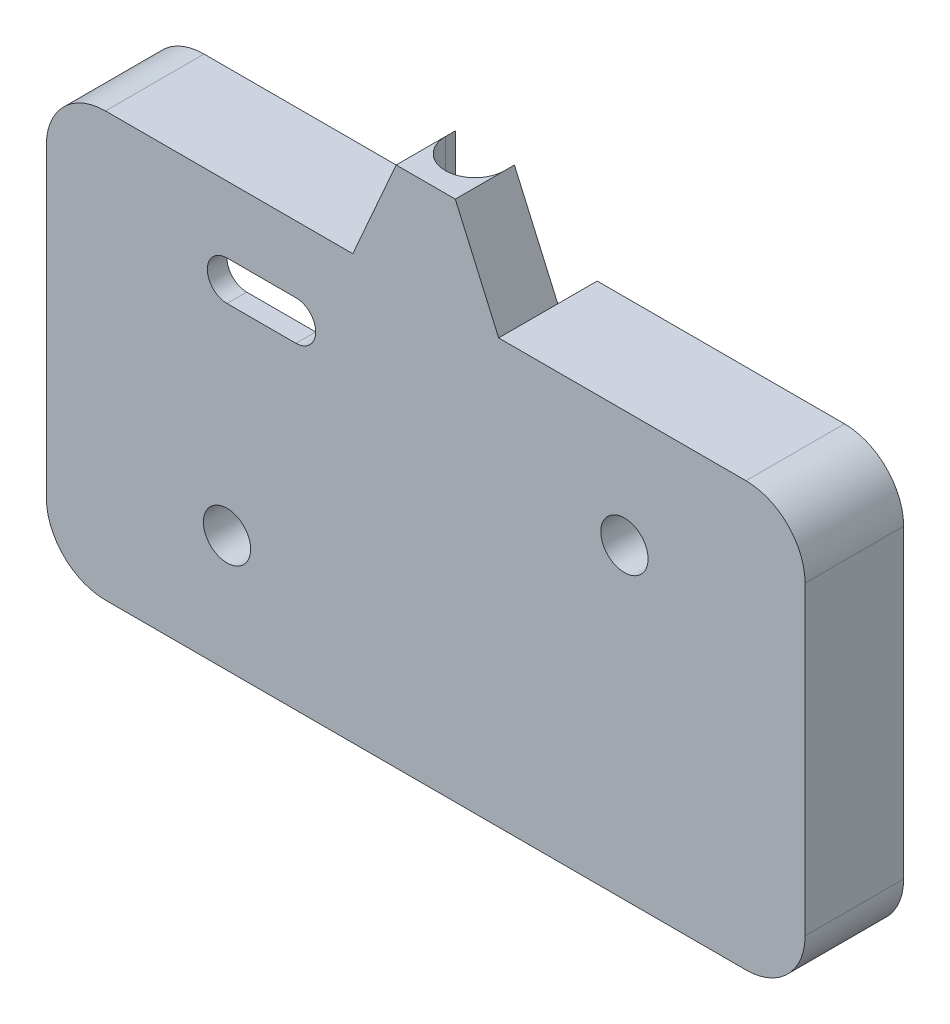
SolidWorks part; units mm, degrees
ref_plane "Přední rovina" through (0, 0, 0) normal (0, 0, 1) x (1, 0, 0)
ref_plane "Horní rovina" through (0, 0, 0) normal (0, 1, 0) x (1, 0, 0)
ref_plane "Pravá rovina" through (0, 0, 0) normal (1, 0, 0) x (0, 0, -1)
sketch "Skica1" plane through (0, 0, 0) normal (0, 0, 1) x (1, 0, 0)
  line L1 (0, 0) -> (38.5, 0)
  line L2 (0, 0) -> (0, 21.5)
  line L3 (0, 21.5) -> (38.5, 21.5)
  line L4 (38.5, 0) -> (38.5, 21.5)
  dimension "D1" = 21.5
  dimension "D2" = 38.5
extrude "Přidat vysunutím1" add sketch "Skica1" along normal blind 1 contours L3 L4 L1 L2
sketch "Skica2" plane through (0, 0, 0) normal (0, 0, -1) x (-1, 0, 0)
  line L1 (-38.5, 21.5) -> (0, 21.5)
  line L2 (-38.5, 21.5) -> (-38.5, 0)
  line L3 (-38.5, 0) -> (0, 0)
  line L4 (0, 21.5) -> (0, 0)
  line L5 (-35.5, 18.5) -> (-3, 18.5)
  line L6 (-35.5, 18.5) -> (-35.5, 3)
  line L7 (-35.5, 3) -> (-3, 3)
  line L8 (-3, 18.5) -> (-3, 3)
  dimension "D1" = 3
  dimension "D2" = 3
  dimension "D3" = 3
  dimension "D4" = 3
extrude "Přidat vysunutím2" add sketch "Skica2" along normal blind 4
fillet "Zaoblit1" radius 3 4 edges at (38.5, 0, -1.5) (0, 0, -1.5) (0, 21.5, -1.5) (38.5, 21.5, -1.5)
sketch "Skica3" plane through (0, 0, 1) normal (0, 0, 1) x (1, 0, 0)
  line L0 (9.1667, 5.921) -> (29.3333, 15.579) construction
  line L1 (19.25, 21.5) -> (19.25, 0) construction
  line L2 (3, 21.5) -> (35.5, 21.5) construction
  line L3 (3, 0) -> (35.5, 0) construction
  line L4 (19.25, 10.75) -> (6.75, 10.75) construction
  circle A0 centre (9.1667, 5.921) radius 1.2
  circle A1 centre (29.3333, 15.579) radius 1.2
  point P10 (19.25, 10.75)
  dimension "D1" = 2.4
  dimension "D2" = 2.4
  dimension "D3" = 22.36
  dimension "D4" = 12.5
  dimension "D5" = 5.4
extrude "Odebrat vysunutím1" cut sketch "Skica3" against normal blind 2
sketch "Skica4" plane through (0, 0, 0) normal (0, 0, -1) x (-1, 0, 0)
  circle A0 centre (-29.3333, 15.579) radius 3
  circle A1 centre (-9.1667, 5.921) radius 3
  circle M3 centre (-9.1667, 5.921) radius 1.2
  circle M4 centre (-29.3333, 15.579) radius 1.2
  line M6 (-35.5, 3) -> (-3, 3)
  line M8 (-3, 18.5) -> (-35.5, 18.5)
  dimension "D1" = 6
  dimension "D2" = 6
extrude "Přidat vysunutím5" add sketch "Skica4" along normal blind 2 contours A0 M8 M4 | A1 M6 M3 region at (31.1448, 13.2943, 0) region at (6.882, 4.1095, 0)
sketch "Skica5" plane through (0, 0, 1) normal (0, 0, 1) x (1, 0, 0)
  line L0 (9.1667, 17.121) -> (12.6667, 17.121) construction
  line L1 (9.1667, 18.121) -> (12.6667, 18.121)
  line L2 (9.1667, 16.121) -> (12.6667, 16.121)
  line L3 (9.1667, 5.921) -> (9.1667, 17.121) construction
  arc A0 (9.1667, 18.121) -> (9.1667, 16.121) centre (9.1667, 17.121) ccw
  arc A1 (12.6667, 16.121) -> (12.6667, 18.121) centre (12.6667, 17.121) ccw
  circle A2 centre (9.1667, 5.921) radius 1.2 construction
  point P2 (10.9167, 17.121)
  dimension "D1" = 11.2
  dimension "D2" = 3.5
  dimension "D3" = 1
extrude "Odebrat vysunutím2" cut sketch "Skica5" against normal blind 2
sketch "Skica7" plane through (0, 0, 1) normal (0, 0, 1) x (1, 0, 0)
  line L0 (15.55, 21.5) -> (17.75, 26.5)
  line L1 (3, 21.5) -> (35.5, 21.5) construction
  line L2 (17.75, 26.5) -> (20.75, 26.5)
  line L3 (20.75, 26.5) -> (22.95, 21.5)
  line L4 (22.95, 21.5) -> (15.55, 21.5)
  point P4 (19.25, 26.5)
  point P7 (19.25, 21.5)
  dimension "D1" = 3
  dimension "D2" = 5
  dimension "D3" = 7.4
  dimension "D4" = 3.7
extrude "Přidat vysunutím6" add sketch "Skica7" against normal blind 1 contours L0 L2 L3 L4
sketch "Skica8" plane through (0, 0, 0) normal (0, 0, -1) x (-1, 0, 0)
  line L0 (-22.95, 21.5) -> (-20.75, 26.5)
  line L1 (-20.75, 26.5) -> (-17.75, 26.5)
  line L2 (-17.75, 26.5) -> (-15.55, 21.5)
  line L3 (-15.55, 21.5) -> (-17.75, 21.5)
  line L4 (-15.55, 21.5) -> (-22.95, 21.5) construction
  line L5 (-17.75, 21.5) -> (-17.75, 26.5)
  line L6 (-17.75, 26.5) -> (-20.75, 26.5)
  line L7 (-20.75, 26.5) -> (-20.75, 21.5)
  line L8 (-20.75, 21.5) -> (-22.95, 21.5)
  point P1 (0, 0)
  point P4 (0, 0)
  line M5 (-22.95, 21.5) -> (-15.55, 21.5)
  line M6 (-15.55, 21.5) -> (-17.75, 26.5)
  line M7 (-17.75, 26.5) -> (-20.75, 26.5)
  line M8 (-20.75, 26.5) -> (-22.95, 21.5)
extrude "Přidat vysunutím7" add sketch "Skica8" along normal blind 2 contours L7 M7 M8 M5 | L5 M5 M6 M7 region at (21.4833, 23.1667, 0) region at (17.0167, 23.1667, 0)
sketch "Skica9" plane through (0, 0, -4) normal (0, 0, -1) x (-1, 0, 0)
  line L0 (-22.95, 21.5) -> (-24.27, 18.5)
  line L1 (-3, 21.5) -> (-35.5, 21.5) construction
  line L2 (-3, 18.5) -> (-35.5, 18.5) construction
  line L3 (-24.27, 18.5) -> (-14.23, 18.5)
  line L4 (-14.23, 18.5) -> (-15.55, 21.5)
  line L5 (-15.55, 21.5) -> (-22.95, 21.5)
  line L6 (-20.75, 26.5) -> (-22.95, 21.5) construction
  line L7 (-15.55, 21.5) -> (-17.75, 26.5) construction
  point P8 (0, 0)
  point P9 (0, 0)
extrude "Odebrat vysunutím5" cut sketch "Skica9" against normal blind 2
sketch "Skica10" plane through (0, 0, -2) normal (0, 0, -1) x (-1, 0, 0)
  line L0 (-20.75, 21.5) -> (-20.75, 18.5)
  line L1 (-24.27, 18.5) -> (-14.23, 18.5) construction
  line L2 (-20.75, 18.5) -> (-17.75, 18.5)
  line L3 (-17.75, 18.5) -> (-17.75, 21.5)
  line L4 (-17.75, 21.5) -> (-20.75, 21.5)
  line L5 (-20.75, 26.5) -> (-20.75, 21.5) construction
  line L6 (-17.75, 21.5) -> (-17.75, 26.5) construction
extrude "Odebrat vysunutím6" cut sketch "Skica10" against normal blind 2
chamfer "Zkosení2" distance 5 angle 30 1 edges at (20.75, 18.5, -1) first distance on face at (20.75, 22.5, -1)
chamfer "Zkosení3" distance 5 angle 30 1 edges at (17.75, 18.5, -1) first distance on face at (17.75, 22.5, -1)
fillet "Zaoblit4" radius 1.5 2 edges at (17.75, 25, 0) (20.75, 25, 0)
